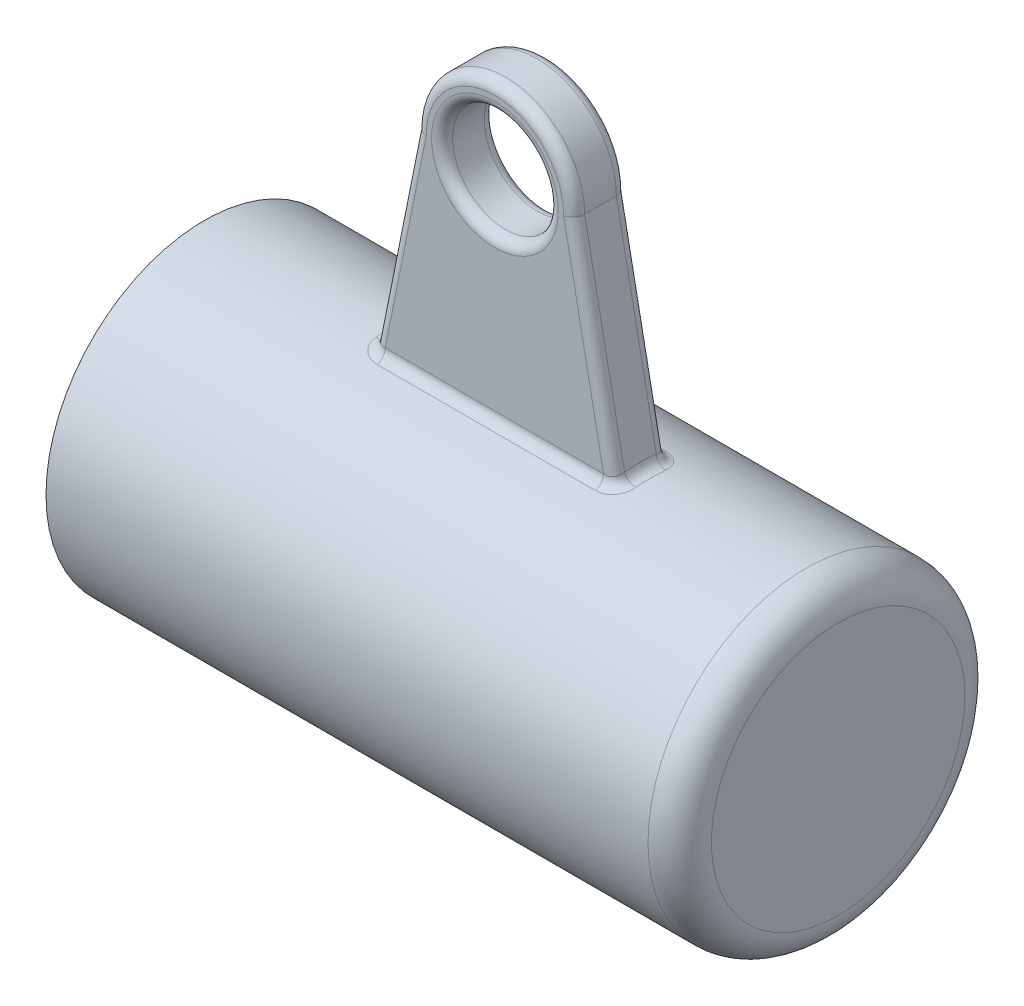
SolidWorks part; units mm, degrees
ref_plane "Front Plane" through (0, 0, 0) normal (0, 0, 1) x (1, 0, 0)
ref_plane "Top Plane" through (0, 0, 0) normal (0, 1, 0) x (1, 0, 0)
ref_plane "Right Plane" through (0, 0, 0) normal (1, 0, 0) x (0, 0, -1)
sketch "Sketch1" plane through (0, 0, 0) normal (1, 0, 0) x (0, 0, -1)
  circle A0 centre (0, 0) radius 15
  dimension "D1" = 30
extrude "Boss-Extrude1" add sketch "Sketch1" along normal mid plane 60
sketch "Sketch2" plane through (-30, 0, 0) normal (-1, 0, 0) x (0, 0, 1)
  circle A0 centre (0, 0) radius 12.5
  dimension "D1" = 25
extrude "Cut-Extrude1" cut sketch "Sketch2" against normal blind 10
sketch "Sketch3" plane through (-20, 0, 0) normal (-1, 0, 0) x (0, 0, 1)
  circle A0 centre (0, 0) radius 6
  dimension "D1" = 12
extrude "Boss-Extrude2" add sketch "Sketch3" along normal mid plane 10
dome "Dome1" faces to dome 1 distance 10 reverse direction no elliptical dome no face at (-25, 0, 6) parameters "D1"=10
fillet "Fillet1" radius 3 1 edges at (-30, 0, 12.5)
fillet "Fillet2" radius 3 1 edges at (30, 0, -15)
sketch "Sketch5" plane through (0, 0, 0) normal (0, 0, 1) x (1, 0, 0)
  line L0 (-7.5, 35) -> (-12, 12.6146)
  line L1 (7.5, 35) -> (12, 12.0595)
  line L2 (-12, 12.6146) -> (12, 12.0595)
  arc A0 (7.5, 35) -> (-7.5, 35) centre (0, 35) ccw
  dimension "D1" = 15
  dimension "D2" = 35
  dimension "D3" = 12
  dimension "D4" = 12
extrude "Boss-Extrude3" add sketch "Sketch5" along normal mid plane 5
sketch "Sketch6" plane through (0, 0, -2.5) normal (0, 0, -1) x (-1, 0, 0)
  circle A0 centre (0, 35) radius 5
  arc A1 (7.5, 35) -> (-7.5, 35) centre (0, 35) ccw construction
  dimension "D1" = 10
extrude "Cut-Extrude2" cut sketch "Sketch6" against normal blind 25
fillet "Fillet3" radius 1 12 edges at (-11.5205, 15, 0) (11.4232, 15, 0) (-9.5313, 24.8951, 2.5) (0, 42.5, 2.5) (9.4822, 24.8951, 2.5) (-0.0492, 14.7902, 2.5) (5, 35, 2.5) (0, 42.5, -2.5) (-9.5313, 24.8951, -2.5) (-0.0492, 14.7902, -2.5) (9.4822, 24.8951, -2.5) (-5, 35, -2.5)
